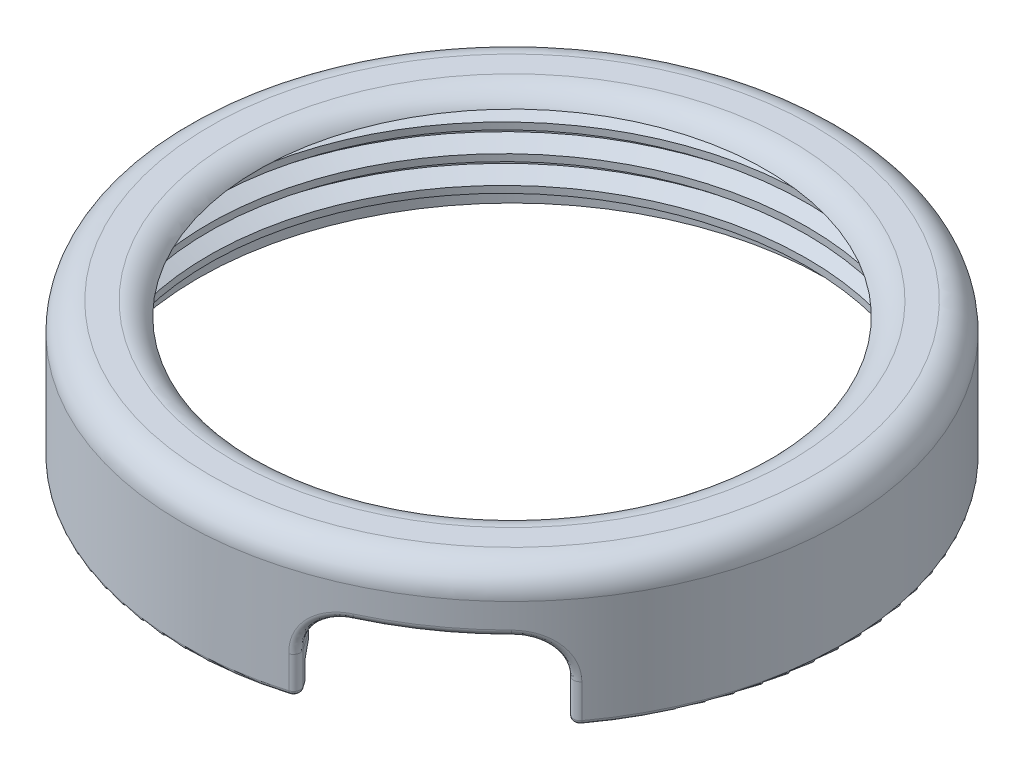
SolidWorks part; units mm, degrees
ref_plane "Front Plane" through (0, 0, 0) normal (0, 0, 1) x (1, 0, 0)
ref_plane "Top Plane" through (0, 0, 0) normal (0, 1, 0) x (1, 0, 0)
ref_plane "Right Plane" through (0, 0, 0) normal (1, 0, 0) x (0, 0, -1)
sketch "Sketch1" plane through (0, 0, 0) normal (0, 1, 0) x (1, 0, 0)
  circle A0 centre (0, 0) radius 24
  dimension "D1" = 48
extrude "Boss-Extrude1" add sketch "Sketch1" along normal blind 10
sketch "Sketch2" plane through (0, 10, 0) normal (0, 1, 0) x (1, 0, 0)
  circle A0 centre (0, 0) radius 22.85
  dimension "D1" = 45.7
extrude "Cut-Extrude1" cut sketch "Sketch2" against normal up to next from offset 1 offset against normal yes
sketch "Sketch3" plane through (0, 10, 0) normal (0, 1, 0) x (1, 0, 0)
  circle A0 centre (0, 0) radius 18.5
  dimension "D1" = 37
extrude "Cut-Extrude2" cut sketch "Sketch3" against normal up to next
thread "Thread1" pitch 2 method extrude profile "Thread Profile1" start angle 0, offset 0, length 0, pitch 2, diameter 45.7
ref_plane "Plane1" through (22.85, 0, 0) normal (0, 0, 1) x (1, 0, 0)
sketch "Thread Profile1" plane through (22.85, 0, 0) normal (0, 0, 1) x (1, 0, 0)
  line L0 (0, 0) -> (0, 2) construction
  line L11 (0, 0) -> (0, 1.75)
  line L12 (0, 1.75) -> (-1.0825, 1.125)
  line L13 (-1.0825, 1.125) -> (-1.0825, 0.625)
  line L15 (-1.0825, 0.625) -> (0, 0)
  line L17 (-1.0825, 0.875) -> (0, 0.875) construction
  point P2 (0, 0)
  dimension "Pitch" = 2
  dimension "Profile_Angle" = 60
  dimension "Profile_Land" = 0.5
  dimension "Profile_Height" = 1.0825
sketch "Sketch6" plane through (0, 10, 0) normal (0, 1, 0) x (1, 0, 0)
  circle A0 centre (0, 0) radius 24
extrude "Cut-Extrude3" cut sketch "Sketch6" along normal blind 2
fillet "Fillet1" radius 2 1 edges at (0, 10, 24)
fillet "Fillet2" radius 2 1 edges at (0, 10, 18.5)
ref_plane "Plane2" through (13.7658, 0, 19.6596) normal (-0.5736, 0, -0.8192) x (0, -1, 0)
sketch "Sketch9" plane through (13.7658, 0, 19.6596) normal (-0.5736, 0, -0.8192) x (0, -1, 0)
  line L0 (0, -7) -> (0, 7)
  line L1 (0, -24) -> (0, 24) construction
  line L2 (0, -7) -> (-2.75, -7)
  line L4 (-2.64, 7) -> (0, 7)
  line L5 (-5.7, -4.05) -> (-5.7, 4.0521)
  arc A0 (-2.75, -7) -> (-5.7, -4.05) centre (-2.75, -4.05) cw
  arc A1 (-2.64, 7) -> (-5.7, 4.0521) centre (-2.75, 4.0521) ccw
  dimension "D3" = 2.95
  dimension "D4" = 2.95
  dimension "D1" = 14
  dimension "D2" = 2.64
  dimension "D5" = 5.7
  dimension "D6" = 2.95
extrude "Cut-Extrude4" cut sketch "Sketch9" along normal up to next
fillet "Fillet3" radius 0.5 5 edges at (7.9613, 4.4473, 22.6411) (13.765, 5.7, 19.6602) (18.1874, 5.0346, 15.6594) (7.4332, 1.32, 22.8199) (18.9014, 1.375, 14.7898)
fillet "Fillet4" radius 0.3 5 edges at (18.3592, 0, 14.0155) (18.9117, 0, 14.4415) (6.8911, 0, 22.0456) (7.1024, 0, 22.7105) (-13.7658, 0, -19.6596)
